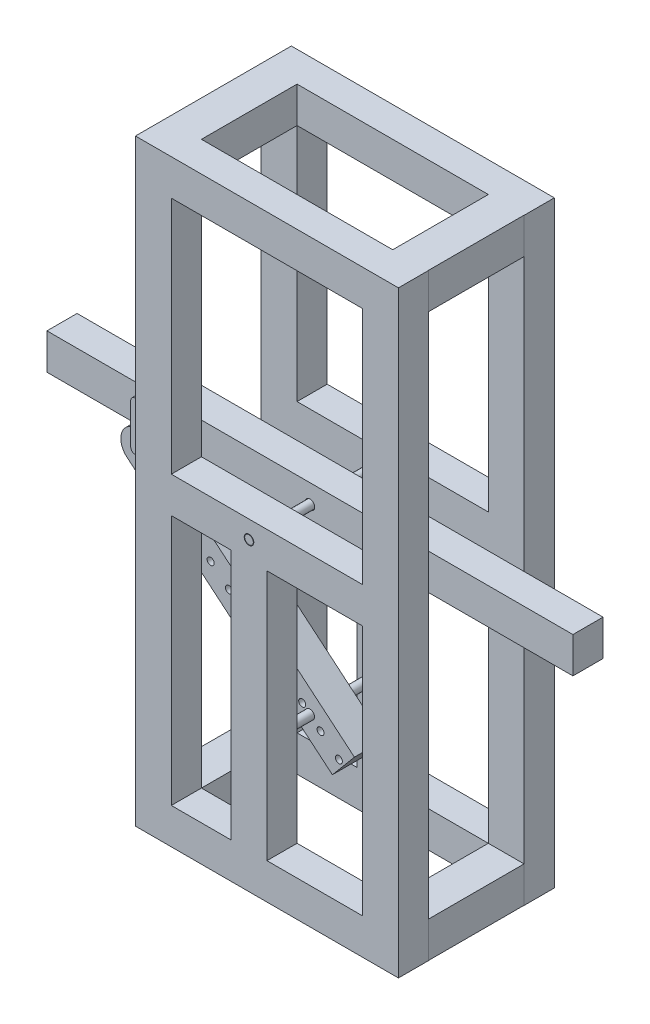
SolidWorks part; units mm, degrees
note: The reader was unsure of these and kept them because the rebuilt part matched: shared geometry of "Esquisse11<3>".
ref_plane "Plan de face" through (0, 0, 0) normal (0, 0, 1) x (1, 0, 0)
ref_plane "Plan de dessus" through (0, 0, 0) normal (0, 1, 0) x (1, 0, 0)
ref_plane "Plan de droite" through (0, 0, 0) normal (1, 0, 0) x (0, 0, -1)
sketch "Esquisse1" plane through (0, 0, 0) normal (0, 0, 1) x (1, 0, 0)
  line L0 (0, 0) -> (0, 1250)
  line L1 (0, 1250) -> (550, 1250)
  line L2 (550, 1250) -> (550, 0)
  line L3 (550, 0) -> (0, 0)
  line L4 (75, 75) -> (200, 75)
  line L5 (200, 75) -> (200, 600)
  line L6 (200, 600) -> (75, 600)
  line L7 (75, 600) -> (75, 75)
  line L8 (275, 75) -> (275, 600)
  line L9 (275, 75) -> (475, 75)
  line L10 (275, 600) -> (475, 600)
  line L11 (475, 75) -> (475, 600)
  line L12 (75, 1175) -> (475, 1175)
  line L13 (75, 1175) -> (75, 675)
  line L14 (475, 1175) -> (475, 675)
  line L15 (75, 675) -> (475, 675)
  line L16 (0, 576.4266) -> (550, 576.4266) construction
  line L17 (275, 0) -> (275, 675) construction
  dimension "D1" = 75
  dimension "D2" = 75
  dimension "D3" = 75
  dimension "D4" = 550
  dimension "D5" = 1250
  dimension "D6" = 75
  dimension "D7" = 75
  dimension "D8" = 500
  dimension "D9" = 75
  dimension "D10" = 75
  dimension "D11" = 75
  dimension "D12" = 75
  dimension "D13" = 200
extrude "Boss.-Extru.1" add sketch "Esquisse1" along normal blind 63
pattern_linear "Répétition linéaire1" count 2 spacing 263 along (0, 0, 1) of "Boss.-Extru.1"
sketch "Esquisse2" plane through (0, 0, 63) normal (0, 0, 1) x (1, 0, 0)
  line L0 (75, 75) -> (75, 0)
  line L1 (75, 75) -> (0, 75)
  line L2 (75, 0) -> (0, 0)
  line L3 (0, 75) -> (0, 0)
  line L4 (0, 0) -> (550, 0) construction
  line L6 (475, 75) -> (475, 0)
  line L7 (475, 75) -> (549.7182, 75)
  line L8 (475, 0) -> (549.7182, 0)
  line L9 (549.7182, 75) -> (549.7182, 0)
  line L10 (475, 1175) -> (475, 1250)
  line L11 (475, 1175) -> (549.7182, 1175)
  line L12 (475, 1250) -> (549.7182, 1250)
  line L13 (549.7182, 1175) -> (549.7182, 1250)
  line L14 (550, 1250) -> (0, 1250) construction
  line L15 (75, 1175) -> (75, 1250)
  line L16 (75, 1175) -> (0, 1175)
  line L17 (75, 1250) -> (0, 1250)
  line L18 (0, 1175) -> (0, 1250)
extrude "Boss.-Extru.2" add sketch "Esquisse2" along normal blind 200
ref_plane "Plan5" through (237.5, 0, 0) normal (-1, 0, 0) x (0, 0, 1)
sketch "Esquisse7" plane through (237.5, 0, 0) normal (-1, 0, 0) x (0, 0, 1)
  line L0 (135.5851, 602.1492) -> (198.5851, 602.1492)
  line L1 (135.5851, 602.1492) -> (135.5851, 677.1492)
  line L2 (198.5851, 602.1492) -> (198.5851, 677.1492)
  line L3 (135.5851, 677.1492) -> (198.5851, 677.1492)
  line L5 (135.5851, 677.1492) -> (198.5851, 602.1492) construction
  line L6 (198.5851, 677.1492) -> (135.5851, 602.1492) construction
  dimension "D1" = 63
  dimension "D2" = 75
sketch "Esquisse8" plane through (475, 0, 0) normal (-1, 0, 0) x (0, 0, 1)
  line L0 (263, 600) -> (63, 675) construction
  line L1 (63, 600) -> (263, 675) construction
extrude "Boss.-Extru.4" add sketch "Esquisse7" along normal blind 550 and the other way blind 550 separate body
sketch "Esquisse3" plane through (0, 0, 326) normal (0, 0, 1) x (1, 0, 0)
  line L0 (75, 675) -> (75, 600) construction
  line L1 (75, 675) -> (475, 675) construction
  line L2 (75, 637.5) -> (476.0322, 637.5) construction
  line L3 (200, 600) -> (275, 675) construction
  circle A0 centre (237.5, 637.5) radius 10
  point P12 (0, 0)
extrude "Enlèv. mat.-Extru.2" cut sketch "Esquisse3" against normal through all
sketch "Esquisse11" plane through (0, 0, 198.5851) normal (0, 0, 1) x (1, 0, 0)
  line L1 (-99.1531, 586.9143) -> (330.5036, 226.557)
  line L2 (-145.2214, 531.9867) -> (284.4353, 171.6294)
  line L3 (330.5036, 226.557) -> (284.4353, 171.6294)
  line L4 (-122.1872, 559.4505) -> (-122.1872, 643.6137) construction
  line L5 (-114.55, 559.4505) -> (-114.55, 643.6137)
  line L7 (-132.34, 643.6137) -> (-132.34, 559.4505)
  arc A0 (-99.1531, 586.9143) -> (-145.2214, 531.9867) centre (-122.1872, 559.4505) ccw
  arc A1 (-132.34, 559.4505) -> (-114.55, 559.4505) centre (-123.445, 559.4505) ccw
  arc A2 (-114.55, 643.6137) -> (-132.34, 643.6137) centre (-123.445, 643.6137) ccw
extrude "Boss.-Extru.5" add sketch "Esquisse11" against normal blind 63 separate body
extrude "Boss.-Extru.6" add sketch "Esquisse11<3>" along normal blind 5
sketch "Esquisse11<3>" plane through (0, 0, 198.5851) normal (0, 0, 1) x (1, 0, 0) same geometry as "Esquisse11"
sketch "Esquisse12" plane through (0, 0, 198.5851) normal (0, 0, 1) x (1, 0, 0)
  line L2 (307.4695, 199.0932) -> (-123.445, 559.4505) construction
  line L3 (330.5036, 226.557) -> (284.4353, 171.6294) construction
  circle A0 centre (-123.445, 559.4505) radius 7.3554
extrude "Enlèv. mat.-Extru.3" cut sketch "Esquisse12" against normal blind 100
pattern_linear "Répétition linéaire2" count 12 spacing 50 along (0.7662, -0.6426, 0) of "Enlèv. mat.-Extru.3"
sketch "Esquisse13" plane through (0, 0, 326) normal (0, 0, 1) x (1, 0, 0)
  line L0 (237.5, 144.65) -> (237.5, -144.65) construction
  circle A0 centre (237.5, 257.6084) radius 9.504
extrude "Boss.-Extru.7" add sketch "Esquisse13" against normal through all
pattern_linear "Répétition linéaire3" count 2 spacing 66 along (0, 0, -1) of "Boss.-Extru.6"
sketch "Esquisse14" plane through (0, 0, 326) normal (0, 0, 1) x (1, 0, 0)
  circle A0 centre (237.5, 637.5) radius 9
extrude "Boss.-Extru.8" add sketch "Esquisse14" against normal blind 326 separate body
